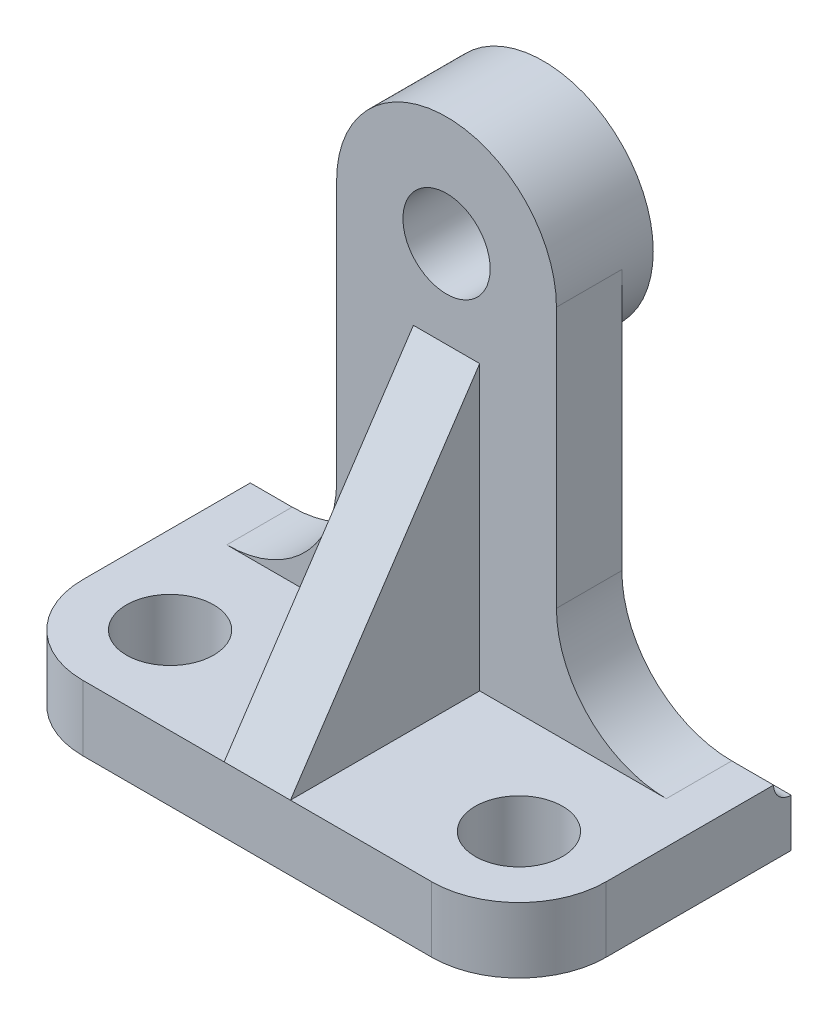
SolidWorks part; units mm, degrees
material "Gray Cast Iron"
ref_plane "Front Plane" through (0, 0, 0) normal (0, 0, 1) x (1, 0, 0)
ref_plane "Top Plane" through (0, 0, 0) normal (0, 1, 0) x (1, 0, 0)
ref_plane "Right Plane" through (0, 0, 0) normal (1, 0, 0) x (0, 0, -1)
sketch "Sketch1" plane through (0, 0, 0) normal (0, 0, 1) x (1, 0, 0)
  line L1 (-38.1, -4.7625) -> (38.1, -4.7625)
  line L2 (-38.1, -4.7625) -> (-38.1, 4.7625)
  line L3 (-38.1, 4.7625) -> (38.1, 4.7625)
  line L4 (38.1, -4.7625) -> (38.1, 4.7625)
  line L5 (-38.1, -4.7625) -> (38.1, 4.7625) construction
  line L6 (-38.1, 4.7625) -> (38.1, -4.7625) construction
  point P0 (0, 0)
  dimension "D1" = 9.525
  dimension "D2" = 76.2
extrude "Boss-Extrude1" add sketch "Sketch1" along normal blind 39.624
fillet "Fillet1" radius 12.7 2 edges at (-38.1, 0, 39.624) (38.1, 0, 39.624)
sketch "Sketch2" plane through (38.1, 0, 0) normal (1, 0, 0) x (0, 0, -1)
  circle A0 centre (0, 4.7625) radius 2.54
  dimension "D1" = 5.08
extrude "Cut-Extrude1" cut sketch "Sketch2" against normal through all
sketch "Sketch3" plane through (0, 4.7625, 0) normal (0, 1, 0) x (1, 0, 0)
  line L5 (38.1, -2.54) -> (-38.1, -2.54) construction
  line L6 (-16.002, -2.54) -> (16.002, -2.54)
  line L7 (-16.002, -2.54) -> (-16.002, -12.065)
  line L8 (-16.002, -12.065) -> (16.002, -12.065)
  line L9 (16.002, -2.54) -> (16.002, -12.065)
  point P5 (0, -2.54)
  dimension "D1" = 9.525
  dimension "D2" = 32.004
extrude "Boss-Extrude2" add sketch "Sketch3" along normal blind 53.975 contours L8 L9 L6 L7
fillet "Fillet2" radius 16.002 1 edges at (-16.002, 4.7625, 7.3025)
fillet "Fillet3" radius 16.002 1 edges at (16.002, 4.7625, 7.3025)
sketch "Sketch4" plane through (0, 0, 12.065) normal (0, 0, 1) x (1, 0, 0)
  line L0 (-16.002, 58.7375) -> (16.002, 58.7375) construction
  circle A0 centre (0, 58.7375) radius 16.002
extrude "Boss-Extrude3" add sketch "Sketch4" against normal blind 14.097
ref_plane "Plane1" through (0, 0, 0) normal (1, 0, 0) x (0, 0, -1)
sketch "Sketch5" plane through (0, 0, 0) normal (1, 0, 0) x (0, 0, -1)
  line L0 (-39.624, 4.7625) -> (-12.065, 4.7625)
  line L1 (-12.065, 4.7625) -> (-12.065, 46.0375)
  line L2 (-12.065, 58.7375) -> (-12.065, 20.7645) construction
  line L3 (-12.065, 46.0375) -> (-39.624, 4.7625)
  dimension "D1" = 41.275
extrude "Boss-Extrude4" add sketch "Sketch5" along normal mid plane 9.652
sketch "Sketch6" plane through (0, 0, 12.065) normal (0, 0, 1) x (1, 0, 0)
  circle A0 centre (0, 58.7375) radius 6.35
  dimension "D1" = 12.7
extrude "Cut-Extrude2" cut sketch "Sketch6" against normal through all
hole_wizard "3/8 (0.5) Diameter Hole1" positions "Sketch7" profile "Sketch8" hole size "3/8" standard "ANSI Inch" end condition through all
sketch "Sketch7" plane through (0, 4.7625, 0) normal (0, 1, 0) x (1, 0, 0)
  point P0 (-25.4, -26.924)
  point P3 (25.4, -26.924)
sketch "Sketch8" plane through (-25.4, 4.7625, 26.924) normal (1, 0, 0) x (0, 0, 1)
  line L0 (0, 0) -> (0, 9.525)
  line L1 (0, 9.525) -> (6.35, 9.525)
  line L2 (6.35, 9.525) -> (6.35, 0)
  line L5 (6.35, 0) -> (0, 0)
  line L11 (0, -6.35) -> (0, 107.95) construction
  dimension "Thru Hole Dia." = 12.7
  dimension "Thru Hole Depth" = 9.525
